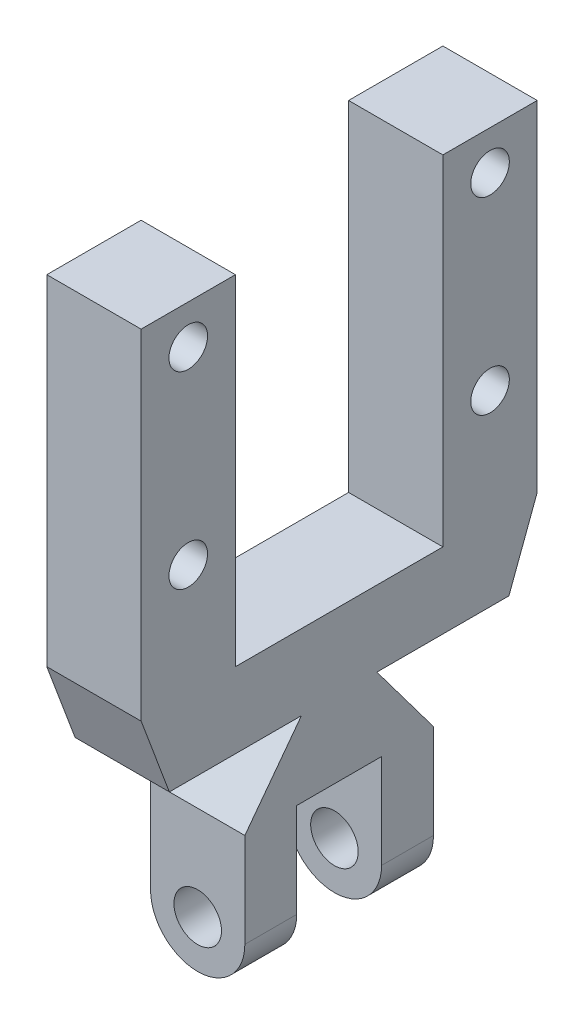
SolidWorks part; units mm, degrees
material "ABS"
ref_plane "Front Plane" through (0, 0, 0) normal (0, 0, 1) x (1, 0, 0)
ref_plane "Top Plane" through (0, 0, 0) normal (0, 1, 0) x (1, 0, 0)
ref_plane "Right Plane" through (0, 0, 0) normal (1, 0, 0) x (0, 0, -1)
sketch "Sketch5" plane through (0, 0, 0) normal (1, 0, 0) x (0, 0, -1)
  line L1 (-11.43, 5.08) -> (-2.54, 5.08)
  line L3 (-13.335, 33.02) -> (-6.985, 33.02)
  line L5 (55, 0) -> (-55, 0) construction
  line L6 (6.35, 0) -> (2.54, 5.08)
  line L7 (-6.35, 0) -> (-2.54, 5.08)
  line L8 (2.54, 5.08) -> (11.43, 5.08)
  line L9 (6.985, 33.02) -> (13.335, 33.02)
  line L10 (-6.985, 10.16) -> (6.985, 10.16)
  line L11 (-6.985, 10.16) -> (-6.985, 33.02)
  line L13 (6.985, 10.16) -> (6.985, 33.02)
  line L14 (-11.43, 5.08) -> (-13.335, 10.16)
  line L15 (-13.335, 10.16) -> (-13.335, 33.02)
  line L16 (11.43, 5.08) -> (13.335, 10.16)
  line L17 (13.335, 10.16) -> (13.335, 33.02)
  line L18 (-6.35, 0) -> (-6.35, -9.525)
  line L19 (-6.35, -9.525) -> (6.35, -9.525)
  line L20 (6.35, -9.525) -> (6.35, 0)
  point P9 (0, -9.525)
  point P14 (0, 10.16)
  dimension "D1" = 22.86
  dimension "D2" = 26.67
  dimension "D3" = 5.08
  dimension "D4" = 12.7
  dimension "D5" = 5.08
  dimension "D6" = 5.08
  dimension "D7" = 6.35
  dimension "D8" = 27.94
  dimension "D9" = 9.525
extrude "Boss-Extrude2" add sketch "Sketch5" along normal blind 6.35
sketch "Sketch14" plane through (0, 0, 6.35) normal (0, 0, 1) x (1, 0, 0)
  line L3 (6.35, 0) -> (6.35, -9.525) construction
  line L4 (0, 0) -> (0, -9.525) construction
  line L5 (6.35, -9.525) -> (0, -9.525) construction
  arc A1 (6.35, -6.35) -> (0, -6.35) centre (3.175, -6.35) cw
extrude "Cut-Extrude1" cut sketch "Sketch14" against normal through all and the other way through all
sketch "Sketch17" plane through (0, 0, 0) normal (0, 0, 1) x (1, 0, 0)
  line L0 (0, 0) -> (0, -6.35) construction
  line L1 (0, 0) -> (6.35, 0)
  line L2 (0, 0) -> (0, -9.525)
  line L3 (0, -9.525) -> (6.35, -9.525)
  line L4 (6.35, 0) -> (6.35, -9.525)
  line L5 (6.35, 0) -> (6.35, -6.35) construction
  arc A0 (0, -6.35) -> (6.35, -6.35) centre (3.175, -6.35) ccw construction
extrude "Cut-Extrude2" cut sketch "Sketch17" against normal mid plane 5.715
hole_wizard "M2 Clearance Hole1" positions "Sketch10" profile "Sketch12" hole size "M2" standard "ANSI Metric" end condition through all
sketch "Sketch10" plane through (6.35, 0, 0) normal (1, 0, 0) x (0, 0, -1)
  point P2 (-10.16, 17.6898)
  point P5 (-10.16, 30.3898)
  point P8 (10.16, 30.3898)
  point P11 (10.16, 17.6898)
sketch "Sketch12" plane through (6.35, 17.6898, 10.16) normal (0, 1, 0) x (0, 0, -1)
  line L0 (0, 0) -> (0, 6.35)
  line L1 (0, 6.35) -> (1.3, 6.35)
  line L2 (1.3, 6.35) -> (1.3, 0)
  line L5 (1.3, 0) -> (0, 0)
  line L11 (0, -6.35) -> (0, 107.95) construction
  dimension "Thru Hole Dia." = 2.6
  dimension "Thru Hole Depth" = 6.35
hole_wizard "M3 Clearance Hole1" positions "Sketch15" profile "Sketch16" hole size "M3" standard "ANSI Metric" end condition through all
sketch "Sketch15" plane through (0, 0, 6.35) normal (0, 0, 1) x (1, 0, 0)
  point P0 (3.175, -6.35)
sketch "Sketch16" plane through (3.175, -6.35, 6.35) normal (1, 0, 0) x (0, -1, 0)
  line L0 (0, 0) -> (0, 19.685)
  line L1 (0, 19.685) -> (1.6, 19.685)
  line L2 (1.6, 19.685) -> (1.6, 0)
  line L5 (1.6, 0) -> (0, 0)
  line L11 (0, -6.35) -> (0, 107.95) construction
  dimension "Thru Hole Dia." = 3.2
  dimension "Thru Hole Depth" = 19.685
